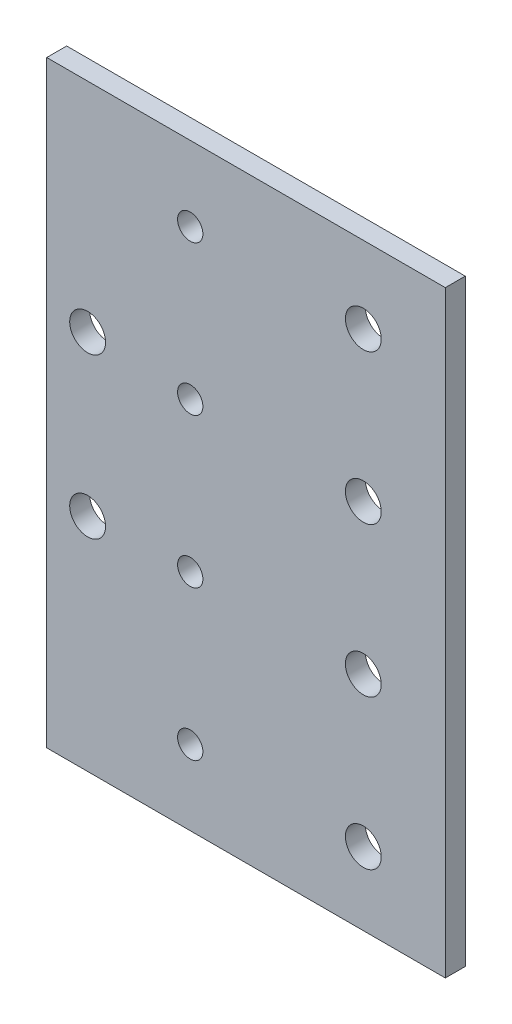
SolidWorks part; units mm, degrees
ref_plane "Front Plane" through (0, 0, 0) normal (0, 0, 1) x (1, 0, 0)
ref_plane "Top Plane" through (0, 0, 0) normal (0, 1, 0) x (1, 0, 0)
ref_plane "Right Plane" through (0, 0, 0) normal (1, 0, 0) x (0, 0, -1)
sketch "Sketch2" plane through (0, 0, 0) normal (0, 0, 1) x (1, 0, 0)
  line L0 (-123.0109, -74.4947) -> (-143.5848, -74.4947) construction
  line L1 (-123.0109, 0.5053) -> (-223.0109, 0.5053)
  line L2 (-123.0109, 0.5053) -> (-123.0109, -149.4947)
  line L3 (-123.0109, -149.4947) -> (-223.0109, -149.4947)
  line L4 (-223.0109, 0.5053) -> (-223.0109, -149.4947)
  line L5 (-143.5848, -74.4947) -> (-143.5848, -56.25) construction
  line L7 (-212.756, -54.0129) -> (-223.0109, -54.0129) construction
  line L8 (-212.756, -94.0129) -> (-223.0109, -94.0129) construction
  line L10 (-143.5848, -56.25) -> (-143.5848, -18.75) construction
  line L11 (-143.5848, -74.4947) -> (-143.5848, -93.75) construction
  line L12 (-143.5848, -93.75) -> (-143.5848, -131.25) construction
  circle A3 centre (-212.756, -54.0129) radius 4.165
  circle A4 centre (-212.756, -94.0129) radius 4.165
  circle A5 centre (-143.5848, -18.75) radius 3.15
  circle A6 centre (-143.5848, -56.25) radius 3.15
  circle A7 centre (-143.5848, -93.75) radius 3.15
  circle A8 centre (-143.5848, -131.25) radius 3.15
  dimension "D1" = 100
  dimension "D2" = 150
extrude "Boss-Extrude1" add sketch "Sketch2" along normal blind 5 contours L4 L3 L2 L1
sketch "Sketch3" plane through (0, 0, 0) normal (0, 0, -1) x (-1, 0, 0)
  circle A3 centre (212.756, -54.0129) radius 4.5
  circle A4 centre (212.756, -94.0129) radius 4.5
  circle A5 centre (143.5848, -18.75) radius 4.5
  circle A6 centre (143.5848, -56.25) radius 4.5
  circle A7 centre (143.5848, -93.75) radius 4.5
  circle A8 centre (143.5848, -131.25) radius 4.5
  dimension "D1" = 9
extrude "Cut-Extrude1" cut sketch "Sketch3" against normal blind 5
sketch "Sketch6" plane through (0, 0, 5) normal (0, 0, 1) x (1, 0, 0)
  line L0 (-223.0109, 0.5053) -> (-187.0109, 0.5053) construction
  line L1 (-187.0109, 0.5053) -> (-187.0109, -149.4947) construction
  line L3 (-187.0109, -149.4947) -> (-187.0109, -74.4947) construction
  line L4 (-187.0109, -74.4947) -> (-187.0109, -111.9947) construction
  line L5 (-187.0109, -111.9947) -> (-187.0109, -93.2447) construction
  line L6 (-187.0109, -111.9947) -> (-187.0109, -149.4947) construction
  line L7 (-187.0109, -149.4947) -> (-187.0109, -130.7447) construction
  line L8 (-187.0109, -74.4947) -> (-187.0109, 0.5053) construction
  line L9 (-187.0109, 0.5053) -> (-187.0109, -36.9947) construction
  line L10 (-187.0109, -36.9947) -> (-187.0109, -18.2447) construction
  line L11 (-187.0109, -36.9947) -> (-187.0109, -74.4947) construction
  line L12 (-187.0109, -74.4947) -> (-187.0109, -55.7447) construction
  line L13 (-223.0109, -149.4947) -> (-187.0109, -149.4947) construction
  circle A0 centre (-187.0109, -18.2447) radius 3.175
  circle A1 centre (-187.0109, -55.7447) radius 3.175
  circle A2 centre (-187.0109, -93.2447) radius 3.175
  circle A3 centre (-187.0109, -130.7447) radius 3.175
  dimension "D1" = 6.35
  dimension "D2" = 36
extrude "Cut-Extrude2" cut sketch "Sketch6" against normal through all
